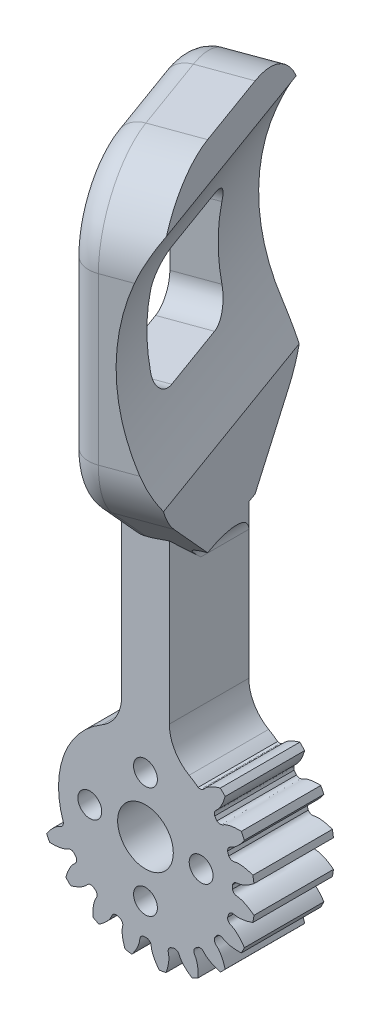
SolidWorks part; units mm, degrees
material "聚脂树脂"
ref_plane "前视基准面" through (0, 0, 0) normal (0, 0, 1) x (1, 0, 0)
ref_plane "上视基准面" through (0, 0, 0) normal (0, 1, 0) x (1, 0, 0)
ref_plane "右视基准面" through (0, 0, 0) normal (1, 0, 0) x (0, 0, -1)
other "Configuration Table"
sketch "草图1" plane through (0, 0, 0) normal (0, 0, 1) x (1, 0, 0)
  circle A0 centre (0, 0) radius 13.75
extrude "凸台-拉伸1" add sketch "草图1" along normal blind 10
ref_axis "基准轴1" through (0, 0, -1.5) along (0, 0, 1)
sketch "草图2" plane through (0, 0, 0) normal (0, 0, 1) x (1, 0, 0)
  line L0 (0, 0) -> (0, 13.75) construction
  circle A0 centre (0, 0) radius 13.75 construction
  arc A1 (0.2416, 10.9348) -> (-0.2416, 10.9348) centre (0, 0) ccw
  arc A2 (3.9764, 15.6228) -> (-3.9764, 15.6228) centre (0, 0) ccw
  spline S0 degree 3 poles (0.2416, 10.9348) (0.764, 11.1168) (0.6964, 11.4839) (0.7661, 11.8375) (0.7736, 11.8719) (0.7829, 11.9108) (0.7941, 11.954) (0.8075, 12.0015) (0.8231, 12.0532) (0.8413, 12.1091) (0.8621, 12.169) (0.8857, 12.2329) (0.9123, 12.3007) (0.9421, 12.3723) (0.9752, 12.4476) (1.0117, 12.5264) (1.0519, 12.6088) (1.0959, 12.6945) (1.1438, 12.7834) (1.1957, 12.8755) (1.2519, 12.9705) (1.3125, 13.0684) (1.3775, 13.1691) (1.4472, 13.2723) (1.5216, 13.3779) (1.601, 13.4858) (1.6853, 13.5958) (1.7747, 13.7078) (1.8694, 13.8216) (1.9693, 13.937) (2.0748, 14.0539) (2.1857, 14.1721) (2.3023, 14.2914) (2.4246, 14.4116) (2.5527, 14.5326) (2.6866, 14.6542) (2.8265, 14.7761) (2.9725, 14.8983) (3.1245, 15.0204) (3.2826, 15.1424) (3.4469, 15.2639) (3.6768, 15.427) (3.8549, 15.5454) (3.9764, 15.6228) knots 0 0 0 0 0.165916 0.170906 0.176664 0.183189 0.190482 0.198542 0.207371 0.216967 0.22733 0.238462 0.250361 0.263027 0.276462 0.290664 0.305634 0.321371 0.337876 0.355149 0.37319 0.391998 0.411574 0.431917 0.453028 0.474907 0.497554 0.520968 0.54515 0.570099 0.595817 0.622302 0.649554 0.677575 0.706363 0.735918 0.766242 0.797333 0.829191 0.861818 0.895212 0.929373 1 1 1 1
  spline S1 degree 3 poles (-0.2416, 10.9348) (-0.764, 11.1168) (-0.6964, 11.4839) (-0.7661, 11.8375) (-0.7736, 11.8719) (-0.7829, 11.9108) (-0.7941, 11.954) (-0.8075, 12.0015) (-0.8231, 12.0532) (-0.8413, 12.1091) (-0.8621, 12.169) (-0.8857, 12.2329) (-0.9123, 12.3007) (-0.9421, 12.3723) (-0.9752, 12.4476) (-1.0117, 12.5264) (-1.0519, 12.6088) (-1.0959, 12.6945) (-1.1438, 12.7834) (-1.1957, 12.8755) (-1.2519, 12.9705) (-1.3125, 13.0684) (-1.3775, 13.1691) (-1.4472, 13.2723) (-1.5216, 13.3779) (-1.601, 13.4858) (-1.6853, 13.5958) (-1.7747, 13.7078) (-1.8694, 13.8216) (-1.9693, 13.937) (-2.0748, 14.0539) (-2.1857, 14.1721) (-2.3023, 14.2914) (-2.4246, 14.4116) (-2.5527, 14.5326) (-2.6866, 14.6542) (-2.8265, 14.7761) (-2.9725, 14.8983) (-3.1245, 15.0204) (-3.2826, 15.1424) (-3.4469, 15.2639) (-3.6768, 15.427) (-3.8549, 15.5454) (-3.9764, 15.6228) knots 0 0 0 0 0.165916 0.170906 0.176664 0.183189 0.190482 0.198542 0.207371 0.216967 0.22733 0.238462 0.250361 0.263027 0.276462 0.290664 0.305634 0.321371 0.337876 0.355149 0.37319 0.391998 0.411574 0.431917 0.453028 0.474907 0.497554 0.520968 0.54515 0.570099 0.595817 0.622302 0.649554 0.677575 0.706363 0.735918 0.766242 0.797333 0.829191 0.861818 0.895212 0.929373 1 1 1 1
extrude "切除-拉伸1" cut sketch "草图2" along normal through all
pattern_circular "阵列(圆周)1" count 20 every 18 about axis through (0, 0, -1.5) along (0, 0, 1) of "切除-拉伸1"
sketch "草图3" plane through (0, 0, 0) normal (0, 0, 1) x (1, 0, 0)
  circle A0 centre (0, 0) radius 12.5 construction
  dimension "Dn" = 25
sketch "草图6" plane through (0, 0, 0) normal (0, 0, -1) x (-1, 0, 0)
  line L0 (0, 0) -> (0, 65.9124) construction
  line L1 (0, 0) -> (39.45, 0) construction
  line L2 (0, 0) -> (-30.8379, 0) construction
  line L3 (-12.5, 0) -> (-12.5, 56.4778) construction
  line L4 (3, 0) -> (3, 36.1803)
  line L5 (-3, 0) -> (-3, 36.1803)
  line L6 (-3, 36.1803) -> (-3, 74.6745)
  line L7 (-3, 74.6745) -> (-12.5, 58.22) construction
  line L8 (-3, 74.6745) -> (6.3052, 90.7916) construction
  line L9 (-3, 74.6745) -> (0.9722, 81.5545)
  line L10 (-3, 0) -> (3, 0)
  line L11 (-5.8534, 12.4419) -> (-3, 14.0893)
  line L12 (5.8534, 12.4419) -> (3, 14.0893)
  line L13 (-3, 36.1803) -> (3, 36.1803)
  line L14 (-3, 33.0059) -> (3, 33.0059)
  circle A0 centre (0, 0) radius 12.5 construction
  circle A1 centre (-12.5, 58.22) radius 24 construction
  circle A2 centre (-12.5, 58.22) radius 26.9444 construction
  arc A3 (0.9722, 81.5545) -> (3, 36.1803) centre (-12.5, 58.22) cw
  arc A4 (-0.5, 79.0046) -> (-3, 36.1803) centre (-12.5, 58.22) cw
  spline S0 degree 3 poles (2502.66, 1658.782) (-28.7069, -14.6032) (-1.7191, 6.2407) (-4.3931, 11.033) (-4.4189, 11.076) (-4.4589, 11.1387) (-4.5098, 11.2131) (-4.5827, 11.3111) (-4.6712, 11.4208) (-4.7765, 11.541) (-4.8994, 11.6706) (-5.0408, 11.8083) (-5.2016, 11.9528) (-5.3825, 12.1027) (-5.5474, 12.2287) (-5.6899, 12.331) (-28.3078, 27.8963) (-140.1993, -89.1599) (2777.6606, 1130.6237) knots -2.506621 -2.506621 -2.506621 -2.506621 0.165916 0.170906 0.183189 0.190482 0.207371 0.22733 0.250361 0.276462 0.305634 0.337876 0.37319 0.411574 0.453028 0.474907 0.497554 13.91055 13.91055 13.91055 13.91055 only from (-3.6089, 10.325) to (-5.8534, 12.4419) construction
  spline S1 degree 3 poles (-3, 10.4088) (-4.144, 10.1273) (-4.1641, 10.6226) (-4.3931, 11.033) (-4.4189, 11.076) (-4.4589, 11.1387) (-4.5098, 11.2131) (-4.5827, 11.3111) (-4.6712, 11.4208) (-4.7765, 11.541) (-4.8994, 11.6706) (-5.0408, 11.8083) (-5.2016, 11.9528) (-5.3825, 12.1027) (-5.5842, 12.2567) (-5.7442, 12.3691) (-5.8366, 12.4308) (-5.8534, 12.4419) knots -0.047197 -0.047197 -0.047197 -0.047197 0.165916 0.170906 0.183189 0.190482 0.207371 0.22733 0.250361 0.276462 0.305634 0.337876 0.37319 0.411574 0.453028 0.497554 0.507432 0.507432 0.507432 0.507432
  spline S2 degree 3 poles (-2502.66, 1658.782) (28.7069, -14.6032) (1.7191, 6.2407) (4.3931, 11.033) (4.4189, 11.076) (4.4589, 11.1387) (4.5098, 11.2131) (4.5827, 11.3111) (4.6712, 11.4208) (4.7765, 11.541) (4.8994, 11.6706) (5.0408, 11.8083) (5.2016, 11.9528) (5.3825, 12.1027) (5.5474, 12.2287) (5.6899, 12.331) (28.3078, 27.8963) (140.1993, -89.1599) (-2777.6606, 1130.6237) knots -2.014052 -2.014052 -2.014052 -2.014052 0.658484 0.663474 0.675757 0.68305 0.699939 0.719899 0.742929 0.76903 0.798202 0.830445 0.865758 0.904142 0.945597 0.967475 0.990122 14.403118 14.403118 14.403118 14.403118 only from (3.6089, 10.325) to (5.8534, 12.4419) construction
  spline S3 degree 3 poles (3, 10.4088) (4.144, 10.1273) (4.1641, 10.6226) (4.3931, 11.033) (4.4189, 11.076) (4.4589, 11.1387) (4.5098, 11.2131) (4.5827, 11.3111) (4.6712, 11.4208) (4.7765, 11.541) (4.8994, 11.6706) (5.0408, 11.8083) (5.2016, 11.9528) (5.3825, 12.1027) (5.5842, 12.2567) (5.7442, 12.3691) (5.8366, 12.4308) (5.8534, 12.4419) knots 0.445372 0.445372 0.445372 0.445372 0.658484 0.663474 0.675757 0.68305 0.699939 0.719899 0.742929 0.76903 0.798202 0.830445 0.865758 0.904142 0.945597 0.990122 1 1 1 1
  dimension "D1" = 25
  dimension "D4" = 48
  dimension "D5" = 30
  dimension "D2" = 6
  dimension "D3" = 58.22
  dimension "D6" = 60
  dimension "D7" = 60
extrude "凸台-拉伸2" add sketch "草图6" against normal blind 20 and the other way blind 10 contours A3 L9 L6 L5 L10 L4 | S1 L5 L11 | L4 S3 L12 region at (0, 16.503, 0) region at (-3.9534, 12.128, 0) region at (3.9534, 12.128, 0)
sketch "草图7" plane through (3, 0, 0) normal (1, 0, 0) x (0, 0, -1)
  line L0 (0, 0) -> (0, 34)
  line L1 (0, 34) -> (10, 34)
  line L3 (10, 34) -> (10, 0)
  line L4 (10, 0) -> (0, 0) construction
  line L5 (10, 0) -> (10, 10.4088) construction
  line L6 (10, 0) -> (0, 0)
  line L7 (-5, 2.5777) -> (-5, 27.3083) construction
  line L8 (-10, 2.5777) -> (0, 2.5777) construction
  line L9 (-20, 34) -> (-20, 0)
  line L10 (-10, 34) -> (-20, 34)
  line L11 (-10, 0) -> (-10, 34)
  line L12 (-20, 0) -> (-10, 0)
  dimension "D1" = 34
extrude "切除-拉伸3" cut sketch "草图7" against normal blind 32 and the other way blind 10
ref_plane "基准面1" through (12.5, 0, 0) normal (1, 0, 0) x (0, 0, -1)
sketch "草图10" plane through (12.5, 0, 0) normal (1, 0, 0) x (0, 0, -1)
  line L1 (-5, 0.2416) -> (-5, 79.5715) construction
  line L2 (-5, 82.4616) -> (-5, 34.4616)
  line L3 (-10, 0.2416) -> (0, 0.2416) construction
  arc A1 (-5, 82.4616) -> (-5, 34.4616) centre (-5, 58.4616) cw
  dimension "D1" = 24
  dimension "D2" = 58.22
sketch "草图4" plane through (0, 0, 10) normal (0, 0, 1) x (1, 0, 0)
  line L0 (0, 0) -> (0, 14.4175) construction
  line L1 (0, 0) -> (19.7904, 0) construction
  circle A0 centre (0, 0) radius 9
  circle A1 centre (0, 0) radius 3.5
  circle A2 centre (0, 7) radius 1.5
  circle A3 centre (7, 0) radius 1.5
  circle A4 centre (0, -7) radius 1.5
  circle A5 centre (-7, 0) radius 1.5
  dimension "D1" = 18
  dimension "D2" = 7
  dimension "D3" = 3
  dimension "D4" = 3
  dimension "D5" = 7
  dimension "D6" = 7
extrude "切除-拉伸2" cut sketch "草图4" against normal blind 20 contours A1 | A5 | A2 | A3 | A4
sketch "草图13" plane through (0, 0, 0) normal (0, 0, -1) x (-1, 0, 0)
  circle A0 centre (0, 0) radius 10
  circle A1 centre (0, -7) radius 1.5 construction
  circle A2 centre (7, 0) radius 1.5 construction
  circle A3 centre (0, 7) radius 1.5 construction
  circle A5 centre (-7, 0) radius 1.5 construction
  circle A6 centre (0, -7) radius 1.5
  circle A7 centre (7, 0) radius 1.5
  circle A8 centre (0, 7) radius 1.5
  circle A10 centre (-7, 0) radius 1.5
  circle A11 centre (0, 0) radius 1.5
  dimension "D1" = 20
  dimension "D2" = 3
ref_plane "基准面2" through (0, 0, 9) normal (0, 0, 1) x (1, 0, 0)
sketch "草图16" plane through (0, 0, 9) normal (0, 0, 1) x (1, 0, 0)
  circle A0 centre (0, 0) radius 12.5 construction
  dimension "D1" = 25
sketch "草图17" plane through (0, 0, 10) normal (0, 0, 1) x (1, 0, 0)
  line L0 (0, 0) -> (-6.6228, 8.7044)
  line L1 (-6.6228, 8.7044) -> (-11.857, 15.5837)
  line L2 (0, 0) -> (-10.325, -3.6089)
  line L3 (-10.325, -3.6089) -> (-17.9409, -6.2709)
  circle A0 centre (0, 0) radius 10.9375
  arc A1 (-6.2318, 8.9885) -> (-6.6228, 8.7044) centre (0, 0) ccw construction
  circle A2 centre (0, 0) radius 17.5
  dimension "D1" = 35
extrude "切除-拉伸5" cut sketch "草图17" against normal blind 10 contours L1 A2 L3 A0 region at (-12.9643, 3.8979, 10)
sketch "草图18" plane through (0, 0, 0) normal (1, 0, 0) x (0, 0, -1)
  line L0 (-5, 0.2416) -> (-5, 83.1767) construction
  line L1 (-10, 0.2416) -> (0, 0.2416) construction
  circle A0 centre (-5, 58.22) radius 4
  dimension "D1" = 8
  dimension "D2" = 58.22
sketch "草图20" plane through (0, 0, 0) normal (0, 0, -1) x (-1, 0, 0)
  line L0 (-3, 14.0893) -> (-3, 10.518)
  line L1 (3, 14.0893) -> (3, 10.518)
  line L2 (5.8534, 12.4419) -> (3, 14.0893) construction
  line L3 (-5.8534, 12.4419) -> (-3, 14.0893) construction
  line L4 (5.8534, 12.4419) -> (3, 14.0893)
  line L5 (-5.8534, 12.4419) -> (-3, 14.0893)
  circle A0 centre (0, 0) radius 10.9375
  arc A1 (10.325, -3.6089) -> (6.2318, 8.9885) centre (0, 0) ccw construction
  arc A2 (6.6252, 12.0486) -> (5.8534, 12.4419) centre (0, 0) ccw construction
  arc A3 (-5.8534, 12.4419) -> (-6.6252, 12.0486) centre (0, 0) ccw construction
  arc A4 (6.6252, 12.0486) -> (5.8534, 12.4419) centre (0, 0) ccw
  arc A5 (-5.8534, 12.4419) -> (-6.6252, 12.0486) centre (0, 0) ccw
  spline S0 degree 3 poles (1876.625, -698.848) (-20.9969, 12.4766) (4.3246, 5.6774) (6.3437, 10.0391) (6.3633, 10.0853) (6.3905, 10.1545) (6.4208, 10.2394) (6.4573, 10.356) (6.4939, 10.4921) (6.5293, 10.6479) (6.5619, 10.8235) (6.5902, 11.0188) (6.6126, 11.2338) (6.6276, 11.4683) (6.6325, 11.6758) (6.6315, 11.8512) (6.0134, 36.0214) (-118.4428, 55.7409) (1694.3797, -1060.7669) knots -2.172632 -2.172632 -2.172632 -2.172632 0.165916 0.170906 0.183189 0.190482 0.207371 0.22733 0.250361 0.276462 0.305634 0.337876 0.37319 0.411574 0.453028 0.474907 0.497554 12.30377 12.30377 12.30377 12.30377 only from (6.2318, 8.9885) to (6.6252, 12.0486) construction
  spline S1 degree 3 poles (-1876.625, -698.848) (20.9969, 12.4766) (-4.3246, 5.6774) (-6.3437, 10.0391) (-6.3633, 10.0853) (-6.3905, 10.1545) (-6.4208, 10.2394) (-6.4573, 10.356) (-6.4939, 10.4921) (-6.5293, 10.6479) (-6.5619, 10.8235) (-6.5902, 11.0188) (-6.6126, 11.2338) (-6.6276, 11.4683) (-6.6325, 11.6758) (-6.6315, 11.8512) (-6.0134, 36.0214) (118.4428, 55.7409) (-1694.3797, -1060.7669) knots -1.680063 -1.680063 -1.680063 -1.680063 0.658484 0.663474 0.675757 0.68305 0.699939 0.719899 0.742929 0.76903 0.798202 0.830445 0.865758 0.904142 0.945597 0.967475 0.990122 12.796339 12.796339 12.796339 12.796339 only from (-6.2318, 8.9885) to (-6.6252, 12.0486) construction
  spline S2 degree 3 poles (6.2318, 8.9885) (5.9162, 9.4428) (6.1867, 9.7) (6.3437, 10.0391) (6.3633, 10.0853) (6.3905, 10.1545) (6.4208, 10.2394) (6.4573, 10.356) (6.4939, 10.4921) (6.5293, 10.6479) (6.5619, 10.8235) (6.5902, 11.0188) (6.6126, 11.2338) (6.6276, 11.4683) (6.6336, 11.722) (6.6305, 11.9176) (6.6261, 12.0285) (6.6252, 12.0486) knots 0 0 0 0 0.165916 0.170906 0.183189 0.190482 0.207371 0.22733 0.250361 0.276462 0.305634 0.337876 0.37319 0.411574 0.453028 0.497554 0.507432 0.507432 0.507432 0.507432
  spline S3 degree 3 poles (-6.2318, 8.9885) (-5.9162, 9.4428) (-6.1867, 9.7) (-6.3437, 10.0391) (-6.3633, 10.0853) (-6.3905, 10.1545) (-6.4208, 10.2394) (-6.4573, 10.356) (-6.4939, 10.4921) (-6.5293, 10.6479) (-6.5619, 10.8235) (-6.5902, 11.0188) (-6.6126, 11.2338) (-6.6276, 11.4683) (-6.6336, 11.722) (-6.6305, 11.9176) (-6.6261, 12.0285) (-6.6252, 12.0486) knots 0.492568 0.492568 0.492568 0.492568 0.658484 0.663474 0.675757 0.68305 0.699939 0.719899 0.742929 0.76903 0.798202 0.830445 0.865758 0.904142 0.945597 0.990122 1 1 1 1
extrude "切除-拉伸7" cut sketch "草图20" against normal blind 10 contours S3 A0 L0 L5 A5 | A0 S2 A4 L4 L1 region at (4.6909, 11.5198, 0) region at (-4.6909, 11.5198, 0)
fillet "圆角7" radius 5 2 edges at (-3, 10.518, 5) (3, 10.518, 5)
ref_plane "基准面5" through (0, 0, 5) normal (0, 0, 1) x (1, 0, 0)
ref_axis "基准轴2" through (0, -15.9741, 5) along (0, 1, 0)
ref_plane "基准面3" through (1.607, 0, 4.4151) normal (-0.342, 0, -0.9397) x (0, -1, 0)
sketch "草图23" plane through (1.607, 0, 4.4151) normal (-0.342, 0, -0.9397) x (0, -1, 0)
  line L0 (0, 0) -> (0, -29.621) construction
  line L1 (0, 0) -> (-94.2322, 0) construction
  line L3 (-33.0059, 6.2393) -> (-33.0059, -2.8191)
  line L5 (-33.0059, 6.2393) -> (-78.0059, 6.2393)
  line L6 (-78.0059, 6.2393) -> (-78.0059, -2.8191)
  line L8 (-78.0059, -2.8191) -> (-73.0151, -2.8191)
  line L9 (-33.0059, -2.8191) -> (-43.4249, -2.8191)
  circle A0 centre (-58.22, -26) radius 27.5
  dimension "D1" = 55
  dimension "D2" = 58.22
  dimension "D4" = 45
  dimension "D3" = 26
extrude "凸台-拉伸3" add sketch "草图23" along normal blind 15 and the other way blind 15 contours A0 region at (-0.7075, 54.7734, 5.2575)
chamfer "倒角1" distance 10 angle 45 2 edges at (5.1303, 33.0059, 19.0954) (-5.1303, 33.0059, -9.0954)
fillet "圆角8" radius 10 4 edges at (-5.1303, 43.0059, -9.0954) (5.1303, 43.0059, 19.0954) (5.1303, 78.0059, 19.0954) (-5.1303, 78.0059, -9.0954)
fillet "圆角9" radius 3 2 edges at (3, 33.0059, 4.6145) (-3, 33.0059, 5.3855)
fillet "圆角10" radius 3 9 edges at (-7.1753, 36.5414, -1.4716) (-9.126, 43.3212, -6.831) (-1.3367, 36.5415, 14.5698) (0.6139, 43.3212, 19.9292) (0.8743, 57.577, 20.6445) (-0.1275, 75.077, 17.8922) (-4.256, 78.0059, 6.5491) (-8.3846, 75.077, -4.794) (-9.3863, 57.577, -7.5463)
ref_plane "基准面4" through (-1.607, 0, 0.5849) normal (0.9397, 0, -0.342) x (0, -1, 0)
sketch "草图24" plane through (-1.607, 0, 0.5849) normal (0.9397, 0, -0.342) x (0, -1, 0)
  line L0 (-13.7842, -5.7245) -> (-98.6382, -5.7245) construction
  line L1 (-65.72, -13.2245) -> (-50.72, -13.2245)
  line L2 (-65.72, -13.2245) -> (-65.72, 1.7755)
  line L3 (-65.72, 1.7755) -> (-50.72, 1.7755)
  line L4 (-50.72, -13.2245) -> (-50.72, 1.7755)
  line L5 (-65.72, -13.2245) -> (-50.72, 1.7755) construction
  line L6 (-65.72, 1.7755) -> (-50.72, -13.2245) construction
  line L7 (-13.7842, -10.423) -> (-13.7842, -1.0261) construction
  line L8 (0, 0) -> (0, 26.7439) construction
  point P0 (-58.22, -5.7245)
  dimension "D1" = 58.22
  dimension "D2" = 15
  dimension "D3" = 15
extrude "切除-拉伸9" cut sketch "草图24" against normal blind 10 and the other way blind 10
fillet "圆角11" radius 3 4 edges at (-3.7537, 65.72, -0.5232) (-3.7537, 50.72, -0.5232) (1.3766, 50.72, 13.5722) (1.3766, 65.72, 13.5722)
